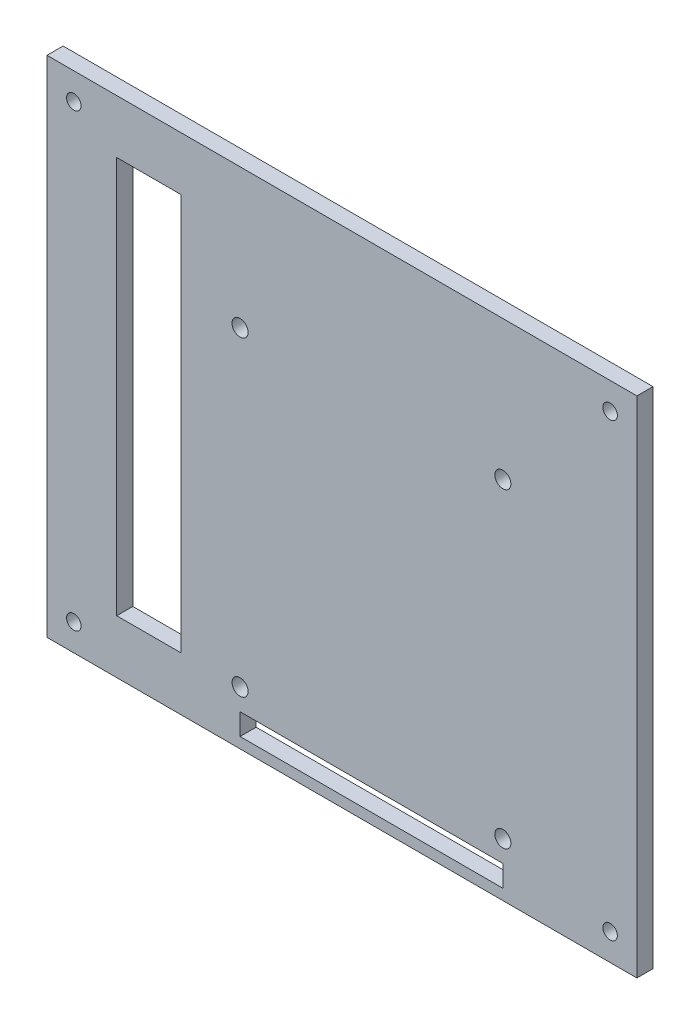
SolidWorks part; units mm, degrees
ref_plane "Alzado" through (0, 0, 0) normal (0, 0, 1) x (1, 0, 0)
ref_plane "Planta" through (0, 0, 0) normal (0, 1, 0) x (1, 0, 0)
ref_plane "Vista lateral" through (0, 0, 0) normal (1, 0, 0) x (0, 0, -1)
sketch "Croquis1" plane through (0, 0, 0) normal (0, 0, 1) x (1, 0, 0)
  line L1 (0, 82) -> (110, 82)
  line L2 (0, 82) -> (0, 0)
  line L3 (0, 0) -> (110, 0)
  line L4 (110, 82) -> (110, 0)
  line L5 (0, 82) -> (110, 82)
  line L9 (0, 0) -> (110, 0)
  dimension "D1" = 110
  dimension "D2" = 82
extrude "Saliente-Extruir1" add sketch "Croquis1" along normal blind 3 contours L1 | L3 | L2 L3 L4 L1 region at (55, 41, 0)
sketch "Croquis7" plane through (0, 82, 0) normal (0, 1, 0) x (1, 0, 0)
  line L1 (0, 0) -> (110, 0)
  line L2 (0, 0) -> (0, -3)
  line L3 (0, -3) -> (110, -3)
  line L4 (110, 0) -> (110, -3)
extrude "Saliente-Extruir2" add sketch "Croquis7" along normal blind 6
sketch "Croquis8" plane through (0, 0, 0) normal (0, -1, 0) x (1, 0, 0)
  line L1 (0, 3) -> (110, 3)
  line L2 (0, 3) -> (0, 0)
  line L3 (0, 0) -> (110, 0)
  line L4 (110, 3) -> (110, 0)
extrude "Saliente-Extruir3" add sketch "Croquis8" along normal blind 6
sketch "Croquis9" plane through (0, 0, 3) normal (0, 0, 1) x (1, 0, 0)
  line L1 (110, 88) -> (110, -6) construction
  line L3 (110, -6) -> (0, -6) construction
  circle A0 centre (97.5, 4) radius 2.5
  dimension "D1" = 5
  dimension "D3" = 10
  dimension "D2" = 12.5
sketch "Croquis11" plane through (0, 0, 3) normal (0, 0, 1) x (1, 0, 0)
  line L0 (0, 83) -> (110, 83) construction
  line L1 (0, 88) -> (0, -6) construction
  line L2 (110, 88) -> (110, -6) construction
  line L3 (5, 88) -> (5, -6) construction
  line L4 (0, 88) -> (110, 88) construction
  line L5 (110, -6) -> (0, -6) construction
  line L6 (105, 88) -> (105, -6) construction
  line L7 (0, -1) -> (110, -1) construction
  dimension "D1" = 5
  dimension "D2" = 5
  dimension "D3" = 5
  dimension "D4" = 5
hole_wizard "Taladro de margen para M2.51" positions "Croquis3D2" profile "Croquis12" hole size "M2.5" standard "ISO" end condition through all
sketch3d "Croquis3D2"
  line L0 (0, 83, 3) -> (110, 83, 3) construction
  line L1 (5, 88, 3) -> (5, -6, 3) construction
  line L2 (0, -1, 3) -> (110, -1, 3) construction
  line L3 (105, 88, 3) -> (105, -6, 3) construction
  point P0 (5, 83, 3)
  point P6 (5, -1, 3)
  point P10 (105, -1, 3)
  point P14 (105, 83, 3)
sketch "Croquis12" plane through (5, 83, 3) normal (1, 0, 0) x (0, -1, 0)
  line L0 (0, 0) -> (0, 3)
  line L1 (0, 3) -> (1.35, 3)
  line L2 (1.35, 3) -> (1.35, 0)
  line L5 (1.35, 0) -> (0, 0)
  line L11 (0, -6.35) -> (0, 107.95) construction
  dimension "Diámetro de taladro hasta el siguiente" = 2.7
  dimension "Profundidad de taladro hasta el siguiente" = 3
sketch "Croquis13" plane through (0, 0, 3) normal (0, 0, 1) x (1, 0, 0)
  line L0 (36, 88) -> (36, -6) construction
  line L1 (110, -6) -> (0, -6) construction
  line L2 (85, 88) -> (85, -6) construction
  line L3 (55, 88) -> (55, -6) construction
  line L4 (0, 88) -> (0, -6) construction
  line L5 (110, 88) -> (110, -6) construction
  line L6 (0, 88) -> (110, 88) construction
  line L7 (0, 62) -> (110, 62) construction
  circle A0 centre (36, 62) radius 1.5
  circle A1 centre (85, 62) radius 1.5
  circle A2 centre (36, 4) radius 1.5
  circle A3 centre (85, 4) radius 1.5
  dimension "D4" = 3
  dimension "D1" = 19
  dimension "D2" = 49
  dimension "D3" = 58
  dimension "D5" = 10
extrude "Cortar-Extruir2" cut sketch "Croquis13" against normal up to next
sketch "Croquis14" plane through (0, 0, 3) normal (0, 0, 1) x (1, 0, 0)
  line L0 (0, 88) -> (0, -6) construction
  line L1 (13, 78) -> (25, 78)
  line L2 (13, 78) -> (13, 4)
  line L3 (13, 4) -> (25, 4)
  line L4 (25, 78) -> (25, 4)
  line L5 (0, 88) -> (110, 88) construction
  line L6 (110, -6) -> (0, -6) construction
  dimension "D1" = 12
  dimension "D2" = 13
  dimension "D3" = 10
  dimension "D4" = 10
extrude "Cortar-Extruir3" cut sketch "Croquis14" against normal up to next
sketch "Croquis15" plane through (0, 0, 3) normal (0, 0, 1) x (1, 0, 0)
  line L0 (110, -6) -> (0, -6) construction
  line L1 (36, 0) -> (85, 0)
  line L2 (36, 0) -> (36, -4)
  line L3 (36, -4) -> (85, -4)
  line L4 (85, 0) -> (85, -4)
  line L6 (85, 5.5) -> (85, -6) construction
  line L7 (36, 5.5) -> (36, -6) construction
  circle A0 centre (85, 4) radius 1.5 construction
  circle A1 centre (36, 4) radius 1.5 construction
  point P16 (55, -6)
  dimension "D1" = 4
  dimension "D2" = 2
extrude "Cortar-Extruir4" cut sketch "Croquis15" against normal up to next
